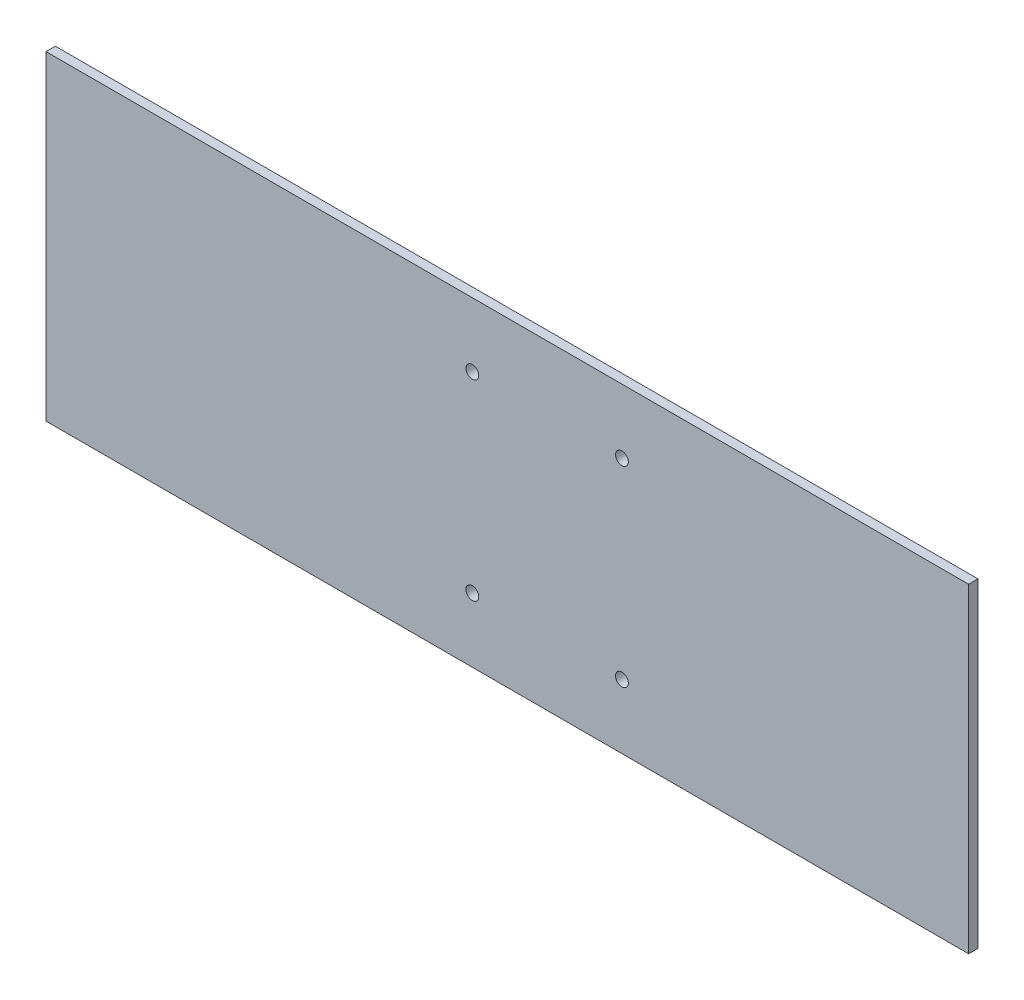
SolidWorks part; units mm, degrees
material "E-Glass Fiber"
ref_plane "Front Plane" through (0, 0, 0) normal (0, 0, 1) x (1, 0, 0)
ref_plane "Top Plane" through (0, 0, 0) normal (0, 1, 0) x (1, 0, 0)
ref_plane "Right Plane" through (0, 0, 0) normal (1, 0, 0) x (0, 0, -1)
sketch "Sketch1" plane through (0, 0, 0) normal (0, 0, 1) x (1, 0, 0)
  line L1 (-117.475, -40.7479) -> (117.475, -40.7479)
  line L2 (-117.475, -40.7479) -> (-117.475, 40.748)
  line L3 (-117.475, 40.748) -> (117.475, 40.748)
  line L4 (117.475, -40.7479) -> (117.475, 40.748)
  line L5 (-117.475, -40.7479) -> (117.475, 40.748) construction
  line L6 (-117.475, 40.748) -> (117.475, -40.7479) construction
  point P0 (0, 0)
  dimension "D1" = 234.95
  dimension "D2" = 81.4959
extrude "Boss-Extrude1" add sketch "Sketch1" along normal blind 2.3813
sketch "Sketch2" plane through (0, 0, 2.3813) normal (0, 0, 1) x (1, 0, 0)
  line L0 (-8.9154, 24.3891) -> (29.1846, 24.3891) construction
  dimension "D1" = 38.1
  dimension "D2" = 24.3891
  dimension "D3" = 8.9154
hole_wizard "#4 Clearance Hole1" positions "Sketch4" profile "Sketch5" hole size "#4" standard "ANSI Inch" end condition through all
sketch "Sketch4" plane through (0, 0, 2.3813) normal (0, 0, 1) x (1, 0, 0)
  point P0 (-8.9154, 24.3891)
  point P3 (29.1846, 24.3891)
sketch "Sketch5" plane through (-8.9154, 24.3891, 2.3813) normal (1, 0, 0) x (0, -1, 0)
  line L0 (0, 0) -> (0, 2.3812)
  line L1 (0, 2.3812) -> (1.6319, 2.3812)
  line L2 (1.6319, 2.3812) -> (1.6319, 0)
  line L5 (1.6319, 0) -> (0, 0)
  line L11 (0, -6.35) -> (0, 107.95) construction
  dimension "Thru Hole Dia." = 3.2639
  dimension "Thru Hole Depth" = 2.3813
mirror "Mirror1" about plane through (0, 0, 0) normal (0, 1, 0) of "#4 Clearance Hole1"
